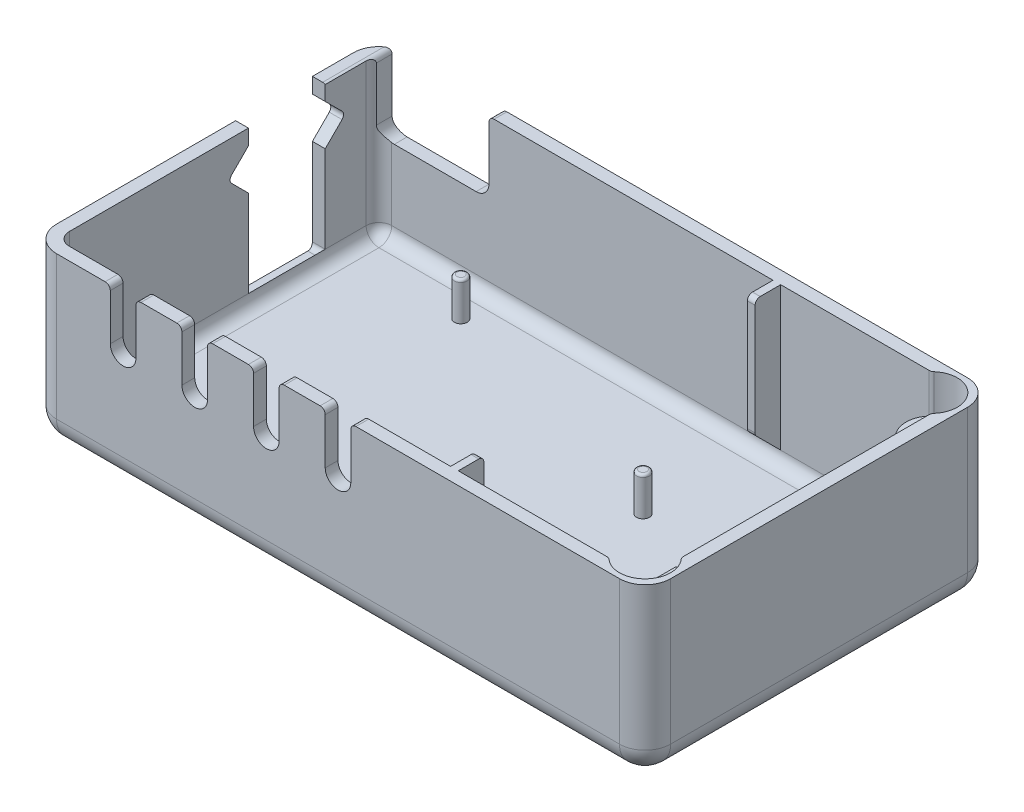
SolidWorks part; units mm, degrees
ref_plane "Front Plane" through (0, 0, 0) normal (0, 0, 1) x (1, 0, 0)
ref_plane "Top Plane" through (0, 0, 0) normal (0, 1, 0) x (1, 0, 0)
ref_plane "Right Plane" through (0, 0, 0) normal (1, 0, 0) x (0, 0, -1)
sketch "Sketch1" plane through (0, 0, 0) normal (0, 1, 0) x (1, 0, 0)
  line L1 (-60, -34) -> (60, -34)
  line L2 (-60, -34) -> (-60, 34)
  line L3 (-60, 34) -> (60, 34)
  line L4 (60, -34) -> (60, 34)
  line L5 (-60, -34) -> (60, 34) construction
  line L6 (-60, 34) -> (60, -34) construction
  point P0 (0, 0)
  dimension "D1" = 120
  dimension "D2" = 68
extrude "Boss-Extrude1" add sketch "Sketch1" along normal blind 33
sketch "Sketch2" plane through (-60, 0, 0) normal (-1, 0, 0) x (0, 0, 1)
  line L0 (-21, 5) -> (-21, 22)
  line L1 (-34, 33) -> (34, 33) construction
  line L2 (-6, 33) -> (-6, 30)
  line L3 (-7, 4) -> (-20, 4)
  line L4 (-21, 22) -> (-25, 26)
  line L5 (-25, 26) -> (-21, 30)
  line L6 (-34, 33) -> (-34, 0) construction
  line L7 (-21, 30) -> (-21, 33)
  line L8 (-34, 0) -> (34, 0) construction
  line L9 (-21, 33) -> (-6, 33)
  line L10 (-6, 30) -> (-2, 26)
  line L11 (-2, 26) -> (-6, 22)
  line L12 (-6, 22) -> (-6, 5)
  arc A1 (-6, 5) -> (-7, 4) centre (-7, 5) cw
  arc A2 (-20, 4) -> (-21, 5) centre (-20, 5) cw
  point P15 (-21, 17.5)
  point P18 (-4, 4)
  point P21 (-19, 4)
  dimension "D5" = 4
  dimension "D1" = 4
  dimension "D2" = 15
  dimension "D3" = 4
  dimension "D4" = 28
  dimension "D6" = 3
  dimension "D7" = 3
fillet "Fillet1" radius 5 8 edges at (0, 0, -34) (-60, 0, 0) (60, 0, 0) (0, 0, 34) (60, 16.5, 34) (-60, 16.5, 34) (-60, 16.5, -34) (60, 16.5, -34)
shell "Shell1" thickness 2.5
extrude "Cut-Extrude2" cut sketch "Sketch2" against normal blind 2.5 contours A1 L3 A2 L0 L4 L5 L7 L9 L2 L10 L11 L12
sketch "Sketch4" plane through (0, 0, 34) normal (0, 0, 1) x (1, 0, 0)
  line L0 (-44.5, 33) -> (-44.5, 23)
  line L1 (-55, 33) -> (55, 33) construction
  line L2 (-39.5, 23) -> (-39.5, 33)
  line L3 (-39.5, 33) -> (-44.5, 33)
  line L4 (55, 0) -> (-55, 0) construction
  line L5 (-60, 5) -> (-60, 33) construction
  line L6 (-30.5, 33) -> (-30.5, 23)
  line L8 (-25.5, 23) -> (-25.5, 33)
  line L9 (-25.5, 33) -> (-30.5, 33)
  line L10 (-16.5, 33) -> (-16.5, 23)
  line L11 (-11.5, 23) -> (-11.5, 33)
  line L12 (-11.5, 33) -> (-16.5, 33)
  line L13 (-2.5, 33) -> (-2.5, 23)
  line L14 (2.5, 23) -> (2.5, 33)
  line L15 (2.5, 33) -> (-2.5, 33)
  arc A0 (-44.5, 23) -> (-39.5, 23) centre (-42, 23) ccw
  arc A1 (-30.5, 23) -> (-25.5, 23) centre (-28, 23) ccw
  arc A2 (-16.5, 23) -> (-11.5, 23) centre (-14, 23) ccw
  arc A3 (-2.5, 23) -> (2.5, 23) centre (0, 23) ccw
  dimension "D4" = 14
  dimension "D1" = 5
  dimension "D2" = 23
  dimension "D3" = 18
  dimension "D5" = 14
  dimension "D6" = 5
  dimension "D7" = 14
  dimension "D8" = 5
  dimension "D9" = 5
extrude "Cut-Extrude5" cut sketch "Sketch4" against normal up to next
sketch "Sketch5" plane through (0, 2.5, 0) normal (0, 1, 0) x (1, 0, 0)
  line L0 (60, -29) -> (60, 29) construction
  line L1 (55, 34) -> (-55, 34) construction
  line L2 (60, 0) -> (-60, 0) construction
  line L3 (-60, 6) -> (-60, -29) construction
  circle A0 centre (54, 28) radius 5
  circle A1 centre (54, -28) radius 5
  dimension "D1" = 10
  dimension "D2" = 6
  dimension "D3" = 6
extrude "Boss-Extrude3" add sketch "Sketch5" along normal up to surface (30.5 mm away) up to face at (7.2846, 33, -6.3471)
fillet "Fillet3" radius 1 8 edges at (-39.5, 33, 32.75) (-44.5, 33, 32.75) (-25.5, 33, 32.75) (-30.5, 33, 32.75) (-11.5, 33, 32.75) (-16.5, 33, 32.75) (2.5, 33, 32.75) (-2.5, 33, 32.75)
sketch "Sketch7" plane through (0, 33, 0) normal (0, 1, 0) x (1, 0, 0)
  circle A0 centre (54, 28) radius 5
  circle A1 centre (54, -28) radius 5
  dimension "D1" = 10
  dimension "D2" = 10
extrude "Cut-Extrude6" cut sketch "Sketch7" against normal blind 7.5
fillet "Fillet4" radius 1 4 edges at (57.5, 29.25, -24.4293) (50.4293, 29.25, -31.5) (50.4293, 29.25, 31.5) (57.5, 29.25, 24.4293)
sketch "Sketch8" plane through (0, 25.5, 0) normal (0, 1, 0) x (1, 0, 0)
  circle A0 centre (54, 28) radius 1.25
  circle A1 centre (54, -28) radius 1.25
  dimension "D1" = 2.5
  dimension "D2" = 2.5
extrude "Cut-Extrude7" cut sketch "Sketch8" against normal blind 10
sketch "Sketch9" plane through (0, 2.5, 0) normal (0, 1, 0) x (1, 0, 0)
  line L0 (-60, 6) -> (-60, -29) construction
  line L3 (55, 34) -> (-55, 34) construction
  circle A0 centre (-35, 25) radius 1.25
  circle A2 centre (15.8, 9.8) radius 1.25
  circle A3 centre (15.8, -18.1) radius 1.25
  dimension "D1" = 2.5
  dimension "D7" = 2.5
  dimension "D8" = 2.5
  dimension "D2" = 25
  dimension "D3" = 9
  dimension "D9" = 27.9
  dimension "D10" = 15.2
  dimension "D11" = 50.8
extrude "Boss-Extrude5" add sketch "Sketch9" along normal blind 7.5
sketch "Sketch12" plane through (0, 0, -34) normal (0, 0, -1) x (-1, 0, 0)
  line L0 (36, 33) -> (36, 21.5)
  line L1 (-55, 33) -> (55, 33) construction
  line L2 (57, 21.5) -> (57, 33)
  line L3 (57, 33) -> (36, 33)
  line L5 (60, 33) -> (60, 5) construction
  line L6 (54.5, 19) -> (38.5, 19)
  arc A0 (54.5, 19) -> (57, 21.5) centre (54.5, 21.5) ccw
  arc A1 (38.5, 19) -> (36, 21.5) centre (38.5, 21.5) cw
  dimension "D4" = 21
  dimension "D2" = 2.5
  dimension "D1" = 14
  dimension "D3" = 3
extrude "Cut-Extrude10" cut sketch "Sketch12" against normal up to next
fillet "Fillet8" radius 0.5 3 edges at (-35, 10, -23.75) (15.8, 10, 19.35) (15.8, 10, -8.55)
fillet "Fillet9" radius 1 2 edges at (-58.75, 26, -2) (-58.75, 26, -25)
fillet "Fillet10" radius 1 4 edges at (-57.3717, 33, -29.7906) (-57, 33, -32.0413) (-36, 33, -32.75) (-57.5, 33, -25)
sketch "Sketch13" plane through (0, 2.5, 0) normal (0, 1, 0) x (1, 0, 0)
  line L0 (57.5, -24.4293) -> (57.5, 24.4293) construction
  line L1 (51, 24.4645) -> (52.5, 24.4645)
  line L2 (51, 24.4645) -> (51, -24.4645)
  line L3 (51, -24.4645) -> (52.5, -24.4645)
  line L4 (52.5, 24.4645) -> (52.5, -24.4645)
  dimension "D1" = 1.5
  dimension "D2" = 5
extrude "Boss-Extrude6" add sketch "Sketch13" along normal up to surface (23 mm away) contours L4 L3 L2 L1 up to face at (54, 25.5, -26.75)
sketch "Sketch14" plane through (0, 25.5, 0) normal (0, 1, 0) x (1, 0, 0)
  line L0 (51, 24) -> (51, -24) construction
  line L1 (51, 18.7523) -> (52.5, 18.7523)
  line L2 (51, 18.7523) -> (51, -18.2477)
  line L3 (51, -18.2477) -> (52.5, -18.2477)
  line L4 (52.5, 18.7523) -> (52.5, -18.2477)
  line L5 (52.5, 23.2303) -> (52.5, -23.2303) construction
  dimension "D1" = 37
extrude "Cut-Extrude12" cut sketch "Sketch14" against normal blind 20 contours L4 L3 L2 L1
fillet "Fillet11" radius 1 4 edges at (51.75, 25.5, 18.2477) (51.75, 5.5, 18.2477) (51.75, 25.5, -18.7523) (51.75, 5.5, -18.7523)
sketch "Sketch17" plane through (0, 0, -31.5) normal (0, 0, 1) x (1, 0, 0)
  line L0 (50.0314, 33) -> (-35, 33) construction
  line L1 (19.5, 33) -> (21, 33)
  line L2 (19.5, 33) -> (19.5, 5)
  line L3 (19.5, 5) -> (21, 5)
  line L4 (21, 33) -> (21, 5)
  line L5 (50.4293, 5) -> (-55, 5) construction
  dimension "D1" = 1.5
  dimension "D2" = 39
extrude "Boss-Extrude7" add sketch "Sketch17" along normal blind 5
chamfer "Chamfer1" distance 5 angle 45 1 edges at (20.25, 5, -26.5)
fillet "Fillet13" radius 1 2 edges at (20.25, 10, -26.5) (20.25, 33, -26.5)
sketch "Sketch18" plane through (0, 0, 31.5) normal (0, 0, -1) x (-1, 0, 0)
  line L0 (-3.5, 33) -> (-50.0314, 33) construction
  line L1 (-21, 33) -> (-19.5, 33)
  line L2 (-21, 33) -> (-21, 5)
  line L3 (-21, 5) -> (-19.5, 5)
  line L4 (-19.5, 33) -> (-19.5, 5)
  line L5 (55, 5) -> (-50.4293, 5) construction
  dimension "D1" = 1.5
  dimension "D2" = 39
extrude "Boss-Extrude8" add sketch "Sketch18" along normal blind 5
chamfer "Chamfer2" distance 5 angle 45 1 edges at (20.25, 5, 26.5)
fillet "Fillet14" radius 1 2 edges at (20.25, 10, 26.5) (20.25, 33, 26.5)
